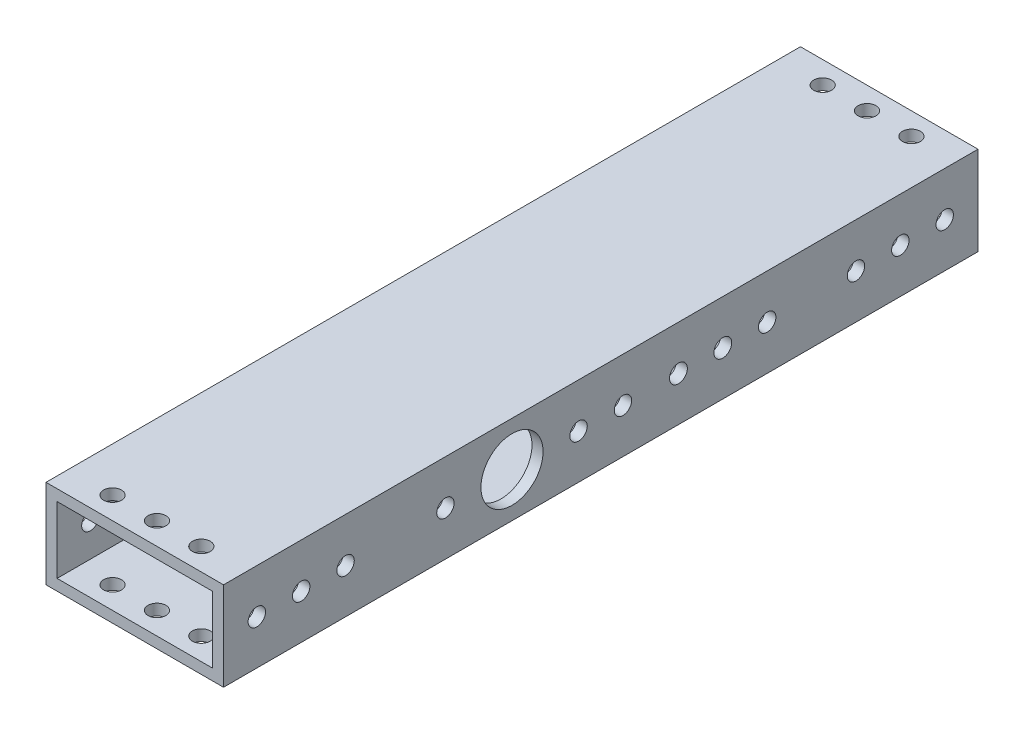
SolidWorks part; units mm, degrees
material "6061-T6 (SS)"
ref_plane "Front Plane" through (0, 0, 0) normal (0, 0, 1) x (1, 0, 0)
ref_plane "Top Plane" through (0, 0, 0) normal (0, 1, 0) x (1, 0, 0)
ref_plane "Right Plane" through (0, 0, 0) normal (1, 0, 0) x (0, 0, -1)
sketch "Sketch1" plane through (0, 0, 0) normal (0, 0, 1) x (1, 0, 0)
  line L0 (-22.225, 9.525) -> (22.225, 9.525)
  line L1 (-25.4, -12.7) -> (25.4, -12.7)
  line L2 (-25.4, -12.7) -> (-25.4, 12.7)
  line L3 (-25.4, 12.7) -> (25.4, 12.7)
  line L4 (25.4, -12.7) -> (25.4, 12.7)
  line L5 (-25.4, -12.7) -> (25.4, 12.7) construction
  line L6 (-25.4, 12.7) -> (25.4, -12.7) construction
  line L7 (22.225, -9.525) -> (22.225, 9.525)
  line L8 (-22.225, -9.525) -> (22.225, -9.525)
  line L9 (-22.225, -9.525) -> (-22.225, 9.525)
  point P0 (0, 0)
  dimension "D1" = 50.8
  dimension "D2" = 25.4
  dimension "D3" = 3.175
extrude "Boss-Extrude1" add sketch "Sketch1" along normal mid plane 215.9
sketch "Sketch3" plane through (0, 12.7, 0) normal (0, 1, 0) x (1, 0, 0)
  line L0 (-25.4, 0) -> (25.4, 0) construction
  line L1 (-25.4, -107.95) -> (-25.4, 107.95) construction
  line L2 (25.4, -107.95) -> (25.4, 107.95) construction
  line L3 (25.4, -107.95) -> (-25.4, -107.95) construction
  circle A0 centre (-12.7, -101.6) radius 2.5527
  circle A1 centre (0, -101.6) radius 2.5527
  circle A2 centre (12.7, -101.6) radius 2.5527
  circle A3 centre (12.7, 101.6) radius 2.5527
  circle A4 centre (0, 101.6) radius 2.5527
  circle A5 centre (-12.7, 101.6) radius 2.5527
  dimension "D1" = 5.1054
  dimension "D2" = 12.7
  dimension "D3" = 12.7
  dimension "D4" = 6.35
extrude "Cut-Extrude2" cut sketch "Sketch3" against normal through all
sketch "Sketch4" plane through (25.4, 0, 0) normal (1, 0, 0) x (0, 0, -1)
  line L0 (-25.4, 0) -> (-45.1908, 0) construction
  line L1 (-16.51, 0) -> (-34.29, 0) construction
  line L8 (-25.4, 0) -> (34.925, 0) construction
  line L9 (0, 12.7) -> (0, -12.7) construction
  line L10 (-107.95, 12.7) -> (107.95, 12.7) construction
  line L11 (-107.95, -12.7) -> (107.95, -12.7) construction
  circle A0 centre (-25.4, 0) radius 8.89
  circle A9 centre (34.925, 0) radius 2.5527
  circle A10 centre (22.225, 0) radius 2.5527
  dimension "D2" = 17.78
  dimension "D3" = 25.4
  dimension "D1" = 60.325
  dimension "D4" = 5.1054
  dimension "D6" = 47.625
extrude "Cut-Extrude3" cut sketch "Sketch4" against normal through all contours A0 | A9 | A10
sketch "Sketch2" plane through (25.4, 0, 0) normal (1, 0, 0) x (0, 0, -1)
  line L0 (-107.95, -12.7) -> (-107.95, 12.7) construction
  line L1 (0, 12.7) -> (0, -12.7) construction
  line L2 (-107.95, 12.7) -> (107.95, 12.7) construction
  line L3 (-107.95, -12.7) -> (107.95, -12.7) construction
  circle A0 centre (-98.425, 0) radius 2.4892
  circle A1 centre (98.425, 0) radius 2.4892
  circle A2 centre (-85.725, 0) radius 2.4892
  circle A3 centre (-73.025, 0) radius 2.4892
  circle A4 centre (73.025, 0) radius 2.4892
  circle A5 centre (85.725, 0) radius 2.4892
  circle A7 centre (-44.45, 0) radius 2.4892
  circle A8 centre (-6.35, 0) radius 2.4892
  circle A9 centre (6.35, 0) radius 2.4892
  circle A10 centre (-25.4, 0) radius 8.89 construction
  circle A11 centre (47.625, 0) radius 2.4892
  circle A12 centre (34.925, 0) radius 2.5527 construction
  dimension "D2" = 4.9784
  dimension "D5" = 4.9784
  dimension "D6" = 19.05
  dimension "D7" = 12.7
  dimension "D8" = 12.7
  dimension "D1" = 9.525
  dimension "D3" = 12.7
  dimension "D4" = 12.7
  dimension ".75" = 19.05
extrude "Cut-Extrude1" cut sketch "Sketch2" against normal through all
sketch "Sketch5" plane through (0, -12.7, 0) normal (0, -1, 0) x (1, 0, 0)
  line L0 (-25.4, 107.95) -> (-25.4, -107.95) construction
  line L1 (-25.4, 107.95) -> (25.4, 107.95) construction
  line L4 (25.4, 25.4) -> (-25.4, 25.4) construction
  line L5 (25.4, 107.95) -> (25.4, -107.95) construction
  circle A0 centre (-3.81, 69.85) radius 2.4892
  circle A1 centre (-16.51, 69.85) radius 2.4892
  circle A2 centre (-16.51, 57.15) radius 2.4892
  circle A3 centre (-3.81, 57.15) radius 2.4892
  circle A8 centre (-3.81, -6.35) radius 2.4892
  circle A9 centre (-16.51, -6.35) radius 2.4892
  circle A10 centre (-16.51, -19.05) radius 2.4892
  circle A11 centre (-3.81, -19.05) radius 2.4892
  dimension "D3" = 4.9784
  dimension "D4" = 8.89
  dimension "D7" = 12.7
  dimension "D12" = 82.55
  dimension "D5" = 31.75
  dimension "D6" = 12.7
  dimension "D1" = 2
  dimension "D2" = 2
extrude "Cut-Extrude4" cut sketch "Sketch5" against normal up to next
